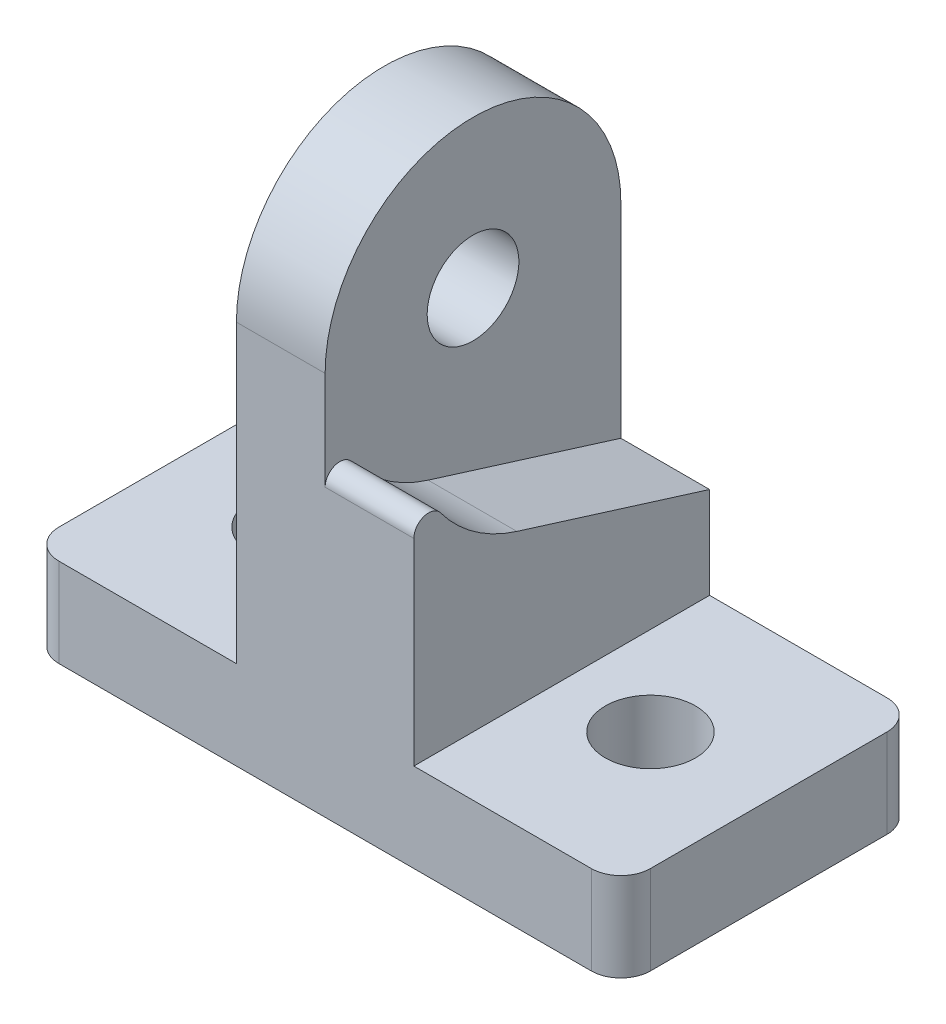
SolidWorks part; units mm, degrees
ref_plane "Front Plane" through (0, 0, 0) normal (0, 0, 1) x (1, 0, 0)
ref_plane "Top Plane" through (0, 0, 0) normal (0, 1, 0) x (1, 0, 0)
ref_plane "Right Plane" through (0, 0, 0) normal (1, 0, 0) x (0, 0, -1)
sketch "Sketch1" plane through (0, 0, 0) normal (0, 1, 0) x (1, 0, 0)
  line L1 (-10, -5) -> (10, -5)
  line L2 (-10, -5) -> (-10, 5)
  line L3 (-10, 5) -> (10, 5)
  line L4 (10, -5) -> (10, 5)
  line L5 (-10, -5) -> (10, 5) construction
  line L6 (-10, 5) -> (10, -5) construction
  circle A0 centre (-6, 0) radius 1.525
  circle A1 centre (6, 0) radius 1.525
  point P0 (0, 0)
  dimension "D3" = 3.05
  dimension "D4" = 3.05
  dimension "D1" = 20
  dimension "D2" = 10
  dimension "D5" = 6
  dimension "D6" = 6
extrude "Boss-Extrude1" add sketch "Sketch1" along normal blind 3
sketch "Sketch2" plane through (0, 3, 0) normal (0, 1, 0) x (1, 0, 0)
  line L0 (10, 5) -> (-10, 5) construction
  line L1 (-3, -5) -> (3, -5)
  line L2 (-3, -5) -> (-3, 5)
  line L3 (-3, 5) -> (3, 5)
  line L4 (3, -5) -> (3, 5)
  line L5 (-3, -5) -> (3, 5) construction
  line L6 (-3, 5) -> (3, -5) construction
  point P0 (0, 0)
  dimension "D1" = 6
extrude "Boss-Extrude2" add sketch "Sketch2" along normal blind 10
sketch "Sketch3" plane through (-3, 0, 0) normal (-1, 0, 0) x (0, 0, 1)
  line L0 (-5, 13) -> (5, 13) construction
  circle A0 centre (0, 13) radius 5
  circle A1 centre (0, 13) radius 1.55
  line M4 (5, 13) -> (-5, 13)
  dimension "D1" = 3.1
extrude "Boss-Extrude3" add sketch "Sketch3" against normal blind 3
extrude "Cut-Extrude1" cut sketch "Sketch3<2>" against normal blind 6 contours A1 M4 region at (-3, 12.3422, 0)
sketch "Sketch3<2>" plane through (-3, 0, 0) normal (-1, 0, 0) x (0, 0, 1) same geometry as "Sketch3"
sketch "Sketch4" plane through (3, 0, 0) normal (1, 0, 0) x (0, 0, -1)
  circle A0 centre (0, 13) radius 5
extrude "Cut-Extrude2" cut sketch "Sketch4" against normal blind 3
fillet "Fillet2" radius 1 4 edges at (-10, 1.5, -5) (10, 1.5, -5) (10, 1.5, 5) (-10, 1.5, 5)
sketch "Sketch5" plane through (3, 0, 0) normal (1, 0, 0) x (0, 0, -1)
  line L0 (5, 13) -> (5, 3) construction
  line L3 (1.005, 8) -> (5, 8)
  line L6 (-5, 13) -> (-5, 3) construction
  line L7 (-5, 11.995) -> (-5, 14.0991)
  line L8 (-5, 14.0991) -> (5, 14.0991)
  line L9 (5, 14.0991) -> (5, 8)
  arc A0 (-5, 11.995) -> (1.005, 8) centre (0, 13) ccw
  dimension "D1" = 10.2
extrude "Cut-Extrude3" cut sketch "Sketch5" against normal blind 3
fillet "Fillet4" radius 0.5 1 edges at (1.5, 11.995, 5)
sketch "Sketch7" plane through (3, 0, 0) normal (1, 0, 0) x (0, 0, -1)
  line L0 (-1.5173, 8.1309) -> (5, 6.1)
  line L4 (-5, 9.6668) -> (-5, 3)
  line L5 (-5, 3) -> (5, 3)
  line L6 (5, 3) -> (5, 8)
  line L7 (5, 8) -> (1.005, 8)
  line L10 (5, 6.1) -> (5, 8)
  line L11 (5, 8) -> (1.005, 8)
  arc A2 (-4.0982, 9.9644) -> (1.005, 8) centre (0, 13) ccw
  arc A3 (-4.0982, 9.9644) -> (-5, 9.6668) centre (-4.5, 9.6668) ccw
  arc A4 (-1.5173, 8.1309) -> (1.005, 8) centre (0, 13) ccw
  dimension "D2" = 1.9
  dimension "D1" = 0
extrude "Cut-Extrude4" cut sketch "Sketch7" against normal blind 3
